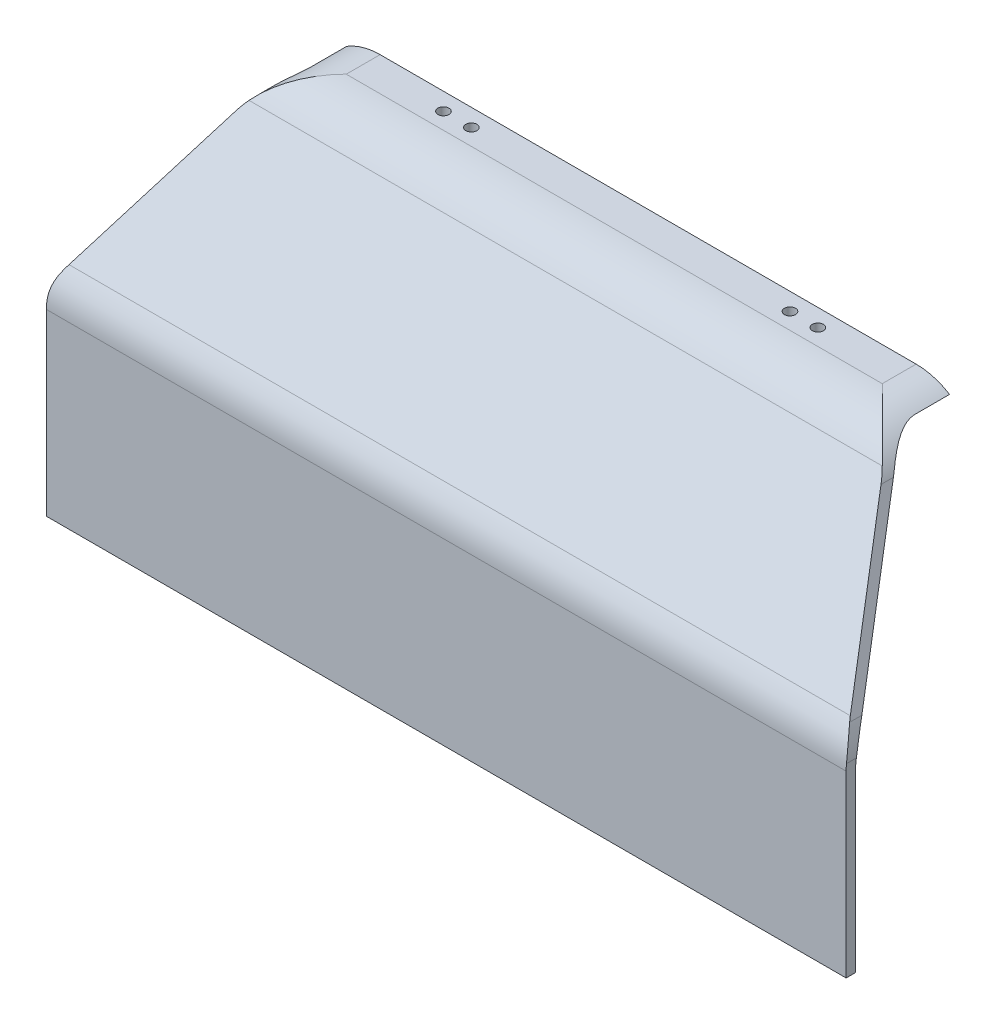
SolidWorks part; units mm, degrees
ref_plane "Alzado" through (0, 0, 0) normal (0, 0, 1) x (1, 0, 0)
ref_plane "Planta" through (0, 0, 0) normal (0, 1, 0) x (1, 0, 0)
ref_plane "Vista lateral" through (0, 0, 0) normal (1, 0, 0) x (0, 0, -1)
sketch "Croquis1" plane through (0, 0, 0) normal (1, 0, 0) x (0, 0, -1)
  line L0 (0, 0) -> (0, 66.9081)
  line L1 (0, 66.9081) -> (41.9998, 116.9615)
  line L2 (41.9998, 116.9615) -> (60.6009, 116.9615)
  line L3 (60.6009, 116.9615) -> (60.6009, 119.9615)
  line L4 (60.6009, 119.9615) -> (40.6009, 119.9615)
  line L5 (40.6009, 119.9615) -> (-3, 68)
  line L6 (-3, 68) -> (-3, 0)
  line L7 (-3, 0) -> (0, 0)
  line L8 (0, 66.9081) -> (29.2398, 66.9081) construction
  dimension "D1" = 3
  dimension "D2" = 3
  dimension "D3" = 3
  dimension "D4" = 68
  dimension "D5" = 119.9615
  dimension "D6" = 20
  dimension "D7" = 50
extrude "Saliente-Extruir1" add sketch "Croquis1" along normal mid plane 252
fillet "Redondeo1" radius 18 1 edges at (0, 68, 3)
fillet "Redondeo2" radius 20 1 edges at (0, 119.9615, -40.6009)
fillet "Redondeo3" radius 17 1 edges at (0, 116.9615, -41.9998)
fillet "Redondeo4" radius 17 1 edges at (0, 66.9081, 0)
sketch "Croquis2" plane through (0, 0, 3) normal (0, 0, 1) x (1, 0, 0)
  line L29 (-96, 119.9615) -> (-126, 68)
  line L35 (-96, 119.9615) -> (-126, 119.9615)
  line L36 (-126, 119.9615) -> (-126, 68)
  dimension "D5" = 60
extrude "Cortar-Extruir1" cut sketch "Croquis2" against normal through all
mirror "Simetría1" about plane through (0, 0, 0) normal (1, 0, 0) of "Cortar-Extruir1"
fillet "Redondeo5" radius 17 2 edges at (-126, 68, 0.064) (126, 68, 0.064)
sketch "Croquis5" plane through (0, 0, -60.6009) normal (0, 0, -1) x (-1, 0, 0)
  line L0 (84.453, 119.9615) -> (96, 119.9615)
  line L1 (96, 119.9615) -> (101.7735, 109.9615)
  arc A0 (101.7735, 109.9615) -> (84.453, 119.9615) centre (84.453, 99.9615) ccw
extrude "Cortar-Extruir2" cut sketch "Croquis5" against normal through all
mirror "Simetría2" about plane through (0, 0, 0) normal (1, 0, 0) of "Cortar-Extruir2"
sketch "Croquis6" plane through (0, 119.9615, 0) normal (0, 1, 0) x (1, 0, 0)
  circle A0 centre (-59, 55.1009) radius 1.75
  circle A1 centre (-50.2, 55.1009) radius 1.75
extrude "Cortar-Extruir3" cut sketch "Croquis6" against normal blind 20
mirror "Simetría3" about plane through (0, 0, 0) normal (1, 0, 0) of "Cortar-Extruir3"
sketch "Croquis7" plane through (0, 0, 0) normal (0, -1, 0) x (1, 0, 0)
  line L4 (-126, 3) -> (-126, 0)
  line L5 (-126, 0) -> (126, 0)
  line L6 (126, 0) -> (126, 3)
  line L7 (126, 3) -> (-126, 3)
  line L8 (-126, 3) -> (-126, 0)
  line L9 (-126, 0) -> (126, 0)
  line L10 (126, 0) -> (126, 3)
  line L11 (126, 3) -> (-126, 3)
  dimension "D1" = 0
extrude "Cortar-Extruir4" cut sketch "Croquis7" against normal blind 5
